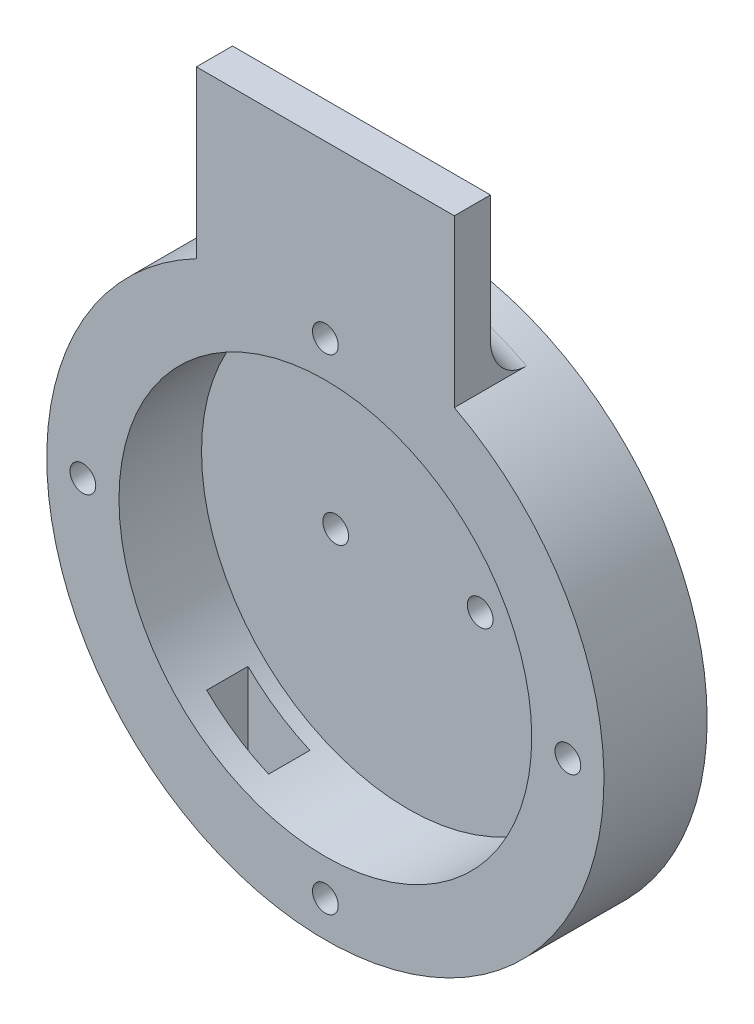
SolidWorks part; units mm, degrees
ref_plane "Front Plane" through (0, 0, 0) normal (0, 0, 1) x (1, 0, 0)
ref_plane "Top Plane" through (0, 0, 0) normal (0, 1, 0) x (1, 0, 0)
ref_plane "Right Plane" through (0, 0, 0) normal (1, 0, 0) x (0, 0, -1)
sketch "Sketch1" plane through (0, 0, 0) normal (0, 0, 1) x (1, 0, 0)
  circle A0 centre (0, 0) radius 27
  circle A1 centre (0, 0) radius 23.5 construction
  circle A2 centre (0, 23.5) radius 1.25
  circle A3 centre (23.5, 0) radius 1.25
  circle A4 centre (0, -23.5) radius 1.25
  circle A5 centre (-23.5, 0) radius 1.25
  circle A6 centre (0, 0) radius 20
  point P15 (0, 0)
  dimension "D1" = 54
  dimension "D2" = 47
  dimension "D3" = 2.5
  dimension "D5" = 40
  dimension "D4" = 4
extrude "Boss-Extrude1" add sketch "Sketch1" along normal blind 10
sketch "Sketch3" plane through (0, 0, 0) normal (0, 0, 1) x (1, 0, 0)
  circle A0 centre (0, 0) radius 20
  circle A1 centre (0, 0) radius 7 construction
  circle A2 centre (-7, 0) radius 1.25
  circle A3 centre (7, 0) radius 1.25
  circle A4 centre (0, 0) radius 11.5 construction
  dimension "D1" = 40
  dimension "D2" = 14
  dimension "D3" = 2.5
  dimension "D4" = 23
extrude "Boss-Extrude2" add sketch "Sketch3" along normal blind 2
sketch "Sketch5" plane through (0, 0, 10) normal (0, 0, 1) x (1, 0, 0)
  line L0 (0, -5.5) -> (0, 5.5) construction
  line L1 (-12.5, 23.9322) -> (-4.2519, 23.9322)
  line L2 (-12.5, 23.9322) -> (-12.5, 40.0322)
  line L3 (-12.5, 40.0322) -> (12.5, 40.0322)
  line L4 (12.5, 23.9322) -> (12.5, 40.0322)
  line L5 (4.2678, 23.9322) -> (0, 26.2545)
  line L6 (0, 26.2545) -> (-4.2519, 23.9322)
  line L7 (4.2678, 23.9322) -> (12.5, 23.9322)
  circle A0 centre (0, 0) radius 27 construction
  point P6 (12.5, 37.9998)
  dimension "D1" = 12.5
  dimension "D2" = 25
  dimension "D3" = 16.1
extrude "Boss-Extrude3" add sketch "Sketch5" against normal blind 3.5
sketch "Sketch4" plane through (0, 0, 0) normal (0, 1, 0) x (1, 0, 0)
  line L0 (27, -10) -> (-27, -10) construction
  line L1 (-14, -3.5) -> (-8, -3.5)
  line L2 (-14, -3.5) -> (-14, -7.5)
  line L3 (-14, -7.5) -> (-8, -7.5)
  line L4 (-8, -3.5) -> (-8, -7.5)
  line L5 (0, -5.5) -> (0, 5.5) construction
  dimension "D1" = 4
  dimension "D2" = 6
  dimension "D3" = 2.5
  dimension "D4" = 8
extrude "Cut-Extrude1" cut sketch "Sketch4" against normal up to surface (25.7876 mm away) up to face at (0, 11.9661, 8.25)
fillet "Fillet1" radius 3.5 1 edges at (0, 27, 6.5)
